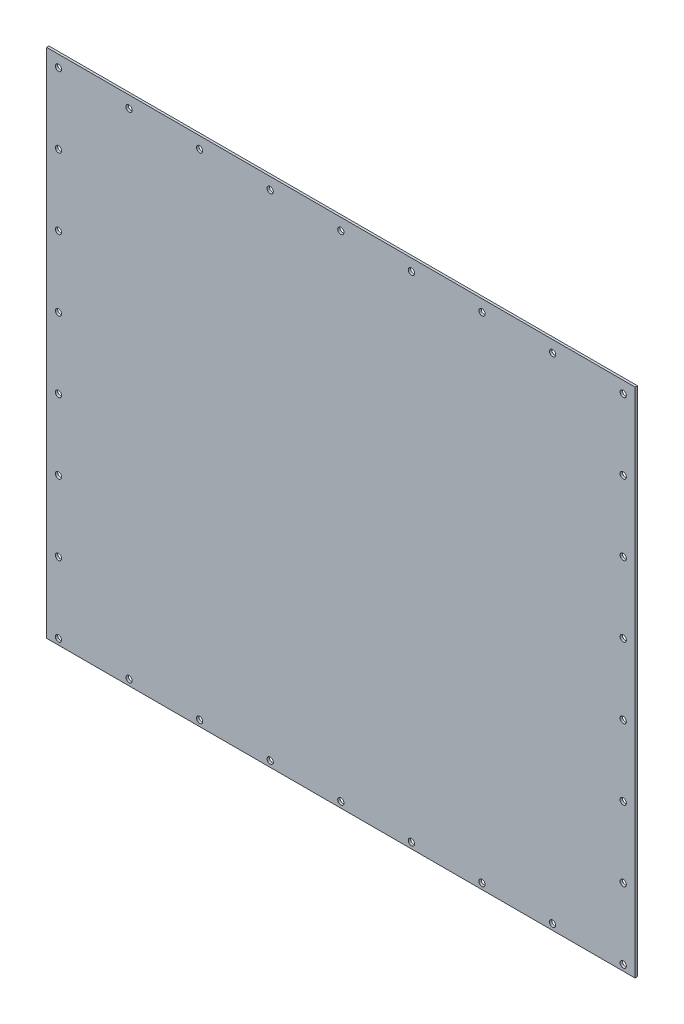
SolidWorks part; units mm, degrees
material "AISI 304"
ref_plane "Front Plane" through (0, 0, 0) normal (0, 0, 1) x (1, 0, 0)
ref_plane "Top Plane" through (0, 0, 0) normal (0, 1, 0) x (1, 0, 0)
ref_plane "Right Plane" through (0, 0, 0) normal (1, 0, 0) x (0, 0, -1)
sketch "Sketch1" plane through (0, 0, 0) normal (0, 0, 1) x (1, 0, 0)
  line L1 (250, -250) -> (-250, -250)
  line L2 (250, -250) -> (250, 250)
  line L3 (250, 250) -> (-250, 250)
  line L4 (-250, -250) -> (-250, 250)
  line L5 (250, -250) -> (-250, 250) construction
  line L6 (250, 250) -> (-250, -250) construction
  point P0 (0, 0)
  dimension "D1" = 500
  dimension "D2" = 500
extrude "Boss-Extrude1" add sketch "Sketch1" along normal mid plane 2
hole_wizard "M5 Clearance Hole2" positions "Sketch2" profile "Sketch3" hole size "M5" standard "ANSI Metric"
sketch "Sketch2" plane through (0, 0, 1) normal (0, 0, 1) x (1, 0, 0)
  line L1 (240, -245) -> (-240, -245)
  line L2 (240, -245) -> (240, 175)
  line L3 (240, 175) -> (-240, 175)
  line L4 (-240, -245) -> (-240, 175)
  line L5 (240, -245) -> (-240, 175) construction
  line L6 (240, 175) -> (-240, -245) construction
  line L7 (-250, -250) -> (250, -250) construction
  line L8 (-250, 250) -> (-250, -250) construction
  line L9 (0, -35) -> (0, -245) construction
  line L10 (250, 250) -> (-250, 250) construction
  point P137 (-240, -245)
  point P142 (0, -35)
  dimension "D1" = 5
  dimension "D2" = 10
  dimension "D3" = 75
sketch "Sketch3" plane through (-240, -245, 1) normal (1, 0, 0) x (0, -1, 0)
  line L0 (0, 0) -> (0, 9.5923)
  line L1 (0, 9.5923) -> (2.65, 8)
  line L2 (2.65, 8) -> (2.65, 0)
  line L5 (2.65, 0) -> (0, 0)
  line L10 (0, 9.5923) -> (-2.65, 8) construction
  line L11 (0, -6.35) -> (0, 107.95) construction
  dimension "Hole Dia." = 5.3
  dimension "Hole Depth" = 8
  dimension "Drill Angle" = 118
sketch "Sketch4" plane through (0, 0, 1) normal (0, 0, 1) x (1, 0, 0)
  line L0 (-242.65, -245) -> (-242.65, -250)
  line L1 (-250, -250) -> (250, -250) construction
  line L2 (-242.65, -250) -> (-237.35, -250)
  line L3 (-237.35, -250) -> (-237.35, -245)
  circle A0 centre (-240, -245) radius 2.65 construction
  arc A1 (-242.65, -245) -> (-237.35, -245) centre (-240, -245) ccw
extrude "Cut-Extrude1" [suppressed] cut sketch "Sketch4" against normal up to surface (2 mm away) up to face at (-237.35, -245, -1)
pattern_linear "LPattern1" count 9 spacing 60 along (1, 0, 0) of "M5 Clearance Hole2"
fillet "Fillet1" [suppressed] radius 1
hole_wizard "M5 Clearance Hole1" positions "Sketch5" profile "Sketch6" hole size "M5" standard "ANSI Metric"
sketch "Sketch5" plane through (0, 0, 1) normal (0, 0, 1) x (1, 0, 0)
  point P0 (-240, 175)
sketch "Sketch6" plane through (-240, 175, 1) normal (1, 0, 0) x (0, -1, 0)
  line L0 (0, 0) -> (0, 9.5923)
  line L1 (0, 9.5923) -> (2.65, 8)
  line L2 (2.65, 8) -> (2.65, 0)
  line L5 (2.65, 0) -> (0, 0)
  line L10 (0, 9.5923) -> (-2.65, 8) construction
  line L11 (0, -6.35) -> (0, 107.95) construction
  dimension "Hole Dia." = 5.3
  dimension "Hole Depth" = 8
  dimension "Drill Angle" = 118
pattern_linear "LPattern2" count 9 spacing 60 along (1, 0, 0) of "M5 Clearance Hole1"
sketch "Sketch7" plane through (0, 0, 1) normal (0, 0, 1) x (1, 0, 0)
  line L0 (-240, 177.65) -> (-250, 177.65)
  line L1 (-250, 250) -> (-250, -250) construction
  line L2 (-250, 177.65) -> (-250, 172.35)
  line L3 (-250, 172.35) -> (-240, 172.35)
  circle A0 centre (-240, 175) radius 2.65 construction
  arc A1 (-240, 177.65) -> (-240, 172.35) centre (-240, 175) ccw
extrude "Cut-Extrude2" [suppressed] cut sketch "Sketch7" against normal up to surface (2 mm away) up to face at (-177.35, 175, -1)
pattern_linear "LPattern3" count 8 spacing 60 along (0, -1, 0) count 2 spacing 60 along (0, 1, 0) of "M5 Clearance Hole1"
mirror "Mirror1" about plane through (0, 0, 0) normal (1, 0, 0) of "LPattern3"
fillet "Fillet2" [suppressed] radius 1
sketch "Sketch8" plane through (0, 0, 1) normal (0, 0, 1) x (1, 0, 0)
  line L0 (250, -250) -> (250, 250) construction
  line L1 (-250, 250) -> (250, 250)
  line L2 (-250, 250) -> (-250, 185)
  line L3 (-250, 185) -> (250, 185)
  line L4 (250, 250) -> (250, 185)
  circle A0 centre (240, 175) radius 2.65 construction
  dimension "D1" = 10
extrude "Cut-Extrude3" cut sketch "Sketch8" against normal up to surface (2 mm away) up to face at (242.65, -185, -1)
